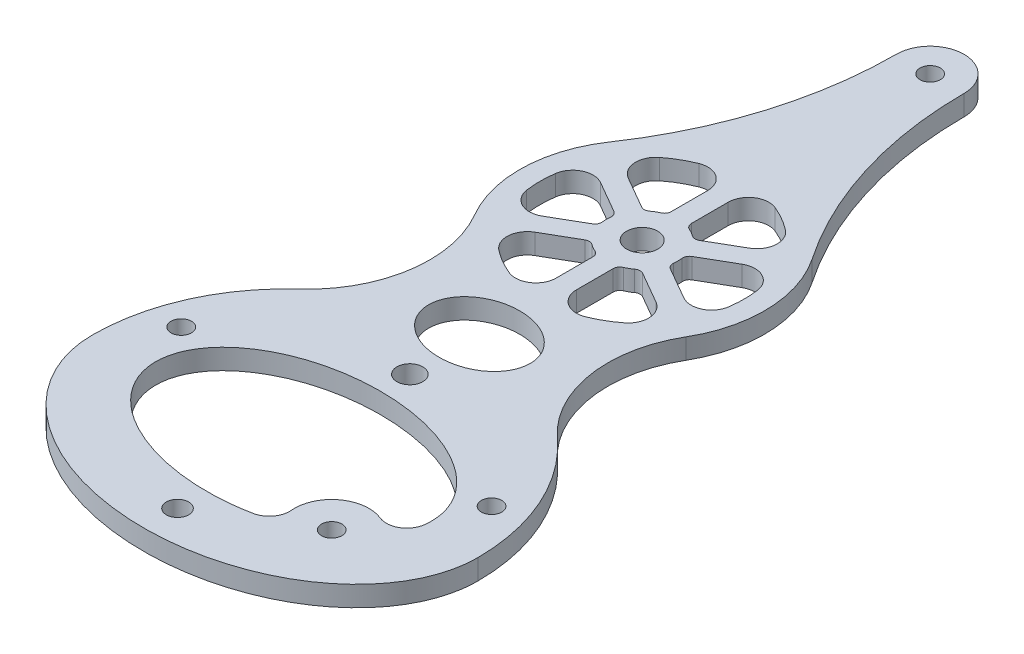
SolidWorks part; units mm, degrees
ref_plane "Front Plane" through (0, 0, 0) normal (0, 0, 1) x (1, 0, 0)
ref_plane "Top Plane" through (0, 0, 0) normal (0, 1, 0) x (1, 0, 0)
ref_plane "Right Plane" through (0, 0, 0) normal (1, 0, 0) x (0, 0, -1)
sketch "Sketch1" plane through (0, 0, 0) normal (0, 1, 0) x (1, 0, 0)
  line L0 (0, -1000) -> (0, 49000) construction
  arc A0 (-14.944, 10.1452) -> (-6.7076, 56.4182) centre (-62.5986, 42.4971) ccw construction
  arc A1 (-14.944, 10.1452) -> (-15.6012, -9.1024) centre (0, 0) ccw construction
  arc A2 (-19.0837, -31.5984) -> (-15.6012, -9.1024) centre (-31.2024, -18.2047) ccw construction
  arc A3 (-19.0837, -31.5984) -> (-28.4436, -52.6898) centre (0, -52.6898) ccw construction
  arc A4 (-14.944, 10.1452) -> (-6.7076, 56.4182) centre (-62.5986, 42.4971) ccw construction
  arc A5 (-14.944, 10.1452) -> (-15.6012, -9.1024) centre (0, 0) ccw
  arc A6 (-19.0837, -31.5984) -> (-15.6012, -9.1024) centre (-31.2024, -18.2047) ccw
  arc A7 (-19.0837, -31.5984) -> (-28.4436, -52.6898) centre (0, -52.6898) ccw
  arc A8 (-14.944, 10.1452) -> (-5, 42.4971) centre (-62.5986, 42.4971) ccw
  arc A9 (-5, 42.4971) -> (5, 42.4971) centre (0, 42.4971) cw
  arc A10 (14.944, 10.1452) -> (5, 42.4971) centre (62.5986, 42.4971) cw
  arc A11 (14.944, 10.1452) -> (15.6012, -9.1024) centre (0, 0) cw
  arc A12 (19.0837, -31.5984) -> (15.6012, -9.1024) centre (31.2024, -18.2047) cw
  arc A13 (19.0837, -31.5984) -> (28.4436, -52.6898) centre (0, -52.6898) cw
  circle A14 centre (22.8961, -45.1123) radius 1.5 construction
  circle A15 centre (-22.8961, -45.1123) radius 1.5 construction
  circle A16 centre (22.8961, -45.1123) radius 1.5
  circle A17 centre (-22.8961, -45.1123) radius 1.5
  circle A18 centre (0, 0) radius 2.3
  circle A19 centre (0, 42.4971) radius 1.5 construction
  circle A20 centre (0, 42.4971) radius 1.5
  circle A21 centre (0, -68.5564) radius 1.65 construction
  circle A22 centre (0, -34.2782) radius 1.9092 construction
  circle A23 centre (0, -68.5564) radius 1.65
  circle A24 centre (0, -34.2782) radius 1.9092
  circle A25 centre (0, 0) radius 2.3 construction
  ellipse E0 centre (0, -52.6898) end of major axis (-28.4436, -52.6898) minor radius 20.8666 (-28.4436, -52.6898) -> (28.4436, -52.6898) ccw construction
  ellipse E1 centre (0, -52.6898) end of major axis (-28.4436, -52.6898) minor radius 20.8666 (-28.4436, -52.6898) -> (28.4436, -52.6898) ccw
  ellipse E2 centre (0, -51.4173) end of major axis (20.3628, -51.4173) minor radius 12.813 construction
  ellipse E3 centre (0, -24.0072) end of major axis (-7.5, -24.0072) minor radius 5.9448 construction
  ellipse E4 centre (0, -51.4173) end of major axis (20.3628, -51.4173) minor radius 12.813
  ellipse E5 centre (0, -24.0072) end of major axis (-7.5, -24.0072) minor radius 5.9448
extrude "Boss-Extrude1" add sketch "Sketch1" along normal blind 3
sketch "Sketch2" plane through (0, 0, 0) normal (0, -1, 0) x (1, 0, 0)
  circle A0 centre (14.1202, 59.9265) radius 5.5
  circle A1 centre (14.1202, 59.9265) radius 8.2743 construction
  dimension "D1" = 11
extrude "Boss-Extrude2" add sketch "Sketch2" against normal up to surface (3 mm away) up to face at (0, 3, 70.2064)
fillet "Fillet1" radius 3 2 edges at (18.5629, 1.5, 56.6842) (9.417, 1.5, 62.7778)
sketch "Sketch3" plane through (0, 3, 0) normal (0, 1, 0) x (1, 0, 0)
  circle A0 centre (14.1202, -59.9265) radius 1.5
  circle A1 centre (14.1202, -59.9265) radius 5.5 construction
  circle A2 centre (-22.8961, -45.1123) radius 1.5 construction
extrude "Cut-Extrude1" cut sketch "Sketch3" against normal through all
sketch "Sketch4" plane through (0, 3, 0) normal (0, 1, 0) x (1, 0, 0)
  line L0 (-1.5, -5.0833) -> (-1.5, -14.9875)
  line L1 (-5.0906, -8.8172) -> (5.0906, -8.8172) construction
  line L2 (5.0906, -8.8172) -> (10.1812, 0) construction
  line L3 (10.1812, 0) -> (5.0906, 8.8172) construction
  line L4 (5.0906, 8.8172) -> (-5.0906, 8.8172) construction
  line L5 (-5.0906, 8.8172) -> (-10.1812, 0) construction
  line L6 (-10.1812, 0) -> (-5.0906, -8.8172) construction
  line L7 (0, -201000) -> (0, 249000) construction
  line L8 (0, 0) -> (-5.0906, -8.8172) construction
  line L9 (-3.6523, -3.8407) -> (-12.2296, -8.7928)
  circle A0 centre (0, 0) radius 8.8172 construction
  circle A1 centre (0, 0) radius 2.3 construction
  circle A2 centre (-5.0906, -8.8172) radius 7.8812 construction
  circle A3 centre (-5.0906, -8.8172) radius 4.8812 construction
  arc A4 (-1.5, -5.0833) -> (-3.6523, -3.8407) centre (0, 0) cw
  circle A5 centre (0, 0) radius 18.0624 construction
  arc A6 (-14.944, 10.1452) -> (-15.6012, -9.1024) centre (0, 0) ccw construction
  arc A7 (-1.5, -14.9875) -> (-12.2296, -8.7928) centre (0, 0) cw
  dimension "D2" = 1.5
  dimension "D1" = 3
extrude "Cut-Extrude2" cut sketch "Sketch4" against normal through all
fillet "Fillet2" radius 3 2 edges at (-1.5, 1.5, 14.9875) (-12.2296, 1.5, 8.7928)
fillet "Fillet3" radius 1 2 edges at (-1.5, 1.5, 5.0833) (-3.6523, 1.5, 3.8407)
pattern_circular "CirPattern1" count 6 over 360 about axis through (0, 3, 0) along (0, -1, 0) of "Fillet2", "Cut-Extrude2", "Fillet3"
